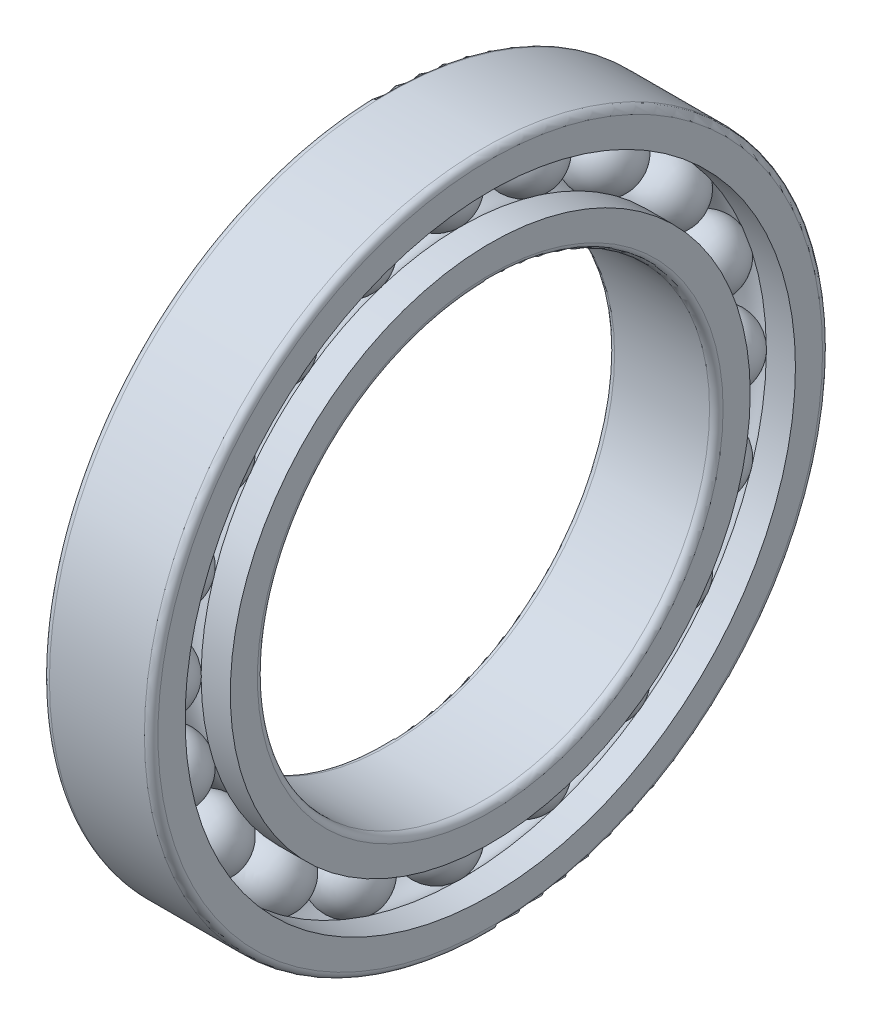
SolidWorks part; units mm, degrees
ref_plane "Plane1" through (0, 0, 0) normal (0, 0, 1) x (1, 0, 0)
ref_plane "Plane2" through (0, 0, 0) normal (0, 1, 0) x (1, 0, 0)
ref_plane "Plane3" through (0, 0, 0) normal (1, 0, 0) x (0, 0, -1)
sketch "Clipboard" plane through (0, 0, 0) normal (0, 0, 1) x (1, 0, 0)
  line L0 (-10, 0) -> (10, 0) construction
  line L1 (0, 0) -> (21.0122, -7.6478)
  line L2 (0, 0) -> (58.7308, 21.3763)
  line L3 (0, 0) -> (21.0122, -7.6478)
  line L4 (0, 0) -> (-22.3573, -0.3902)
  dimension "BallCLRad" = 62.5
sketch "CagSpiSke" plane through (0, 0, 0) normal (0, 0, 1) x (1, 0, 0)
  line L0 (0.75, 61.25) -> (0.75, 63.75)
  line L1 (0.75, 63.75) -> (-0.75, 63.75)
  line L2 (-0.75, 63.75) -> (-0.75, 61.25)
  line L3 (-0.75, 61.25) -> (0.75, 61.25)
  line L4 (-20.6375, 0) -> (20.6375, 0) construction
  line L5 (0, 0) -> (0, 23.7692) construction
  dimension "OD" = 127.5
  dimension "ID" = 122.5
revolve "CageSpine" add sketch "CagSpiSke" angle 0.001 about L4 reverse direction yes
ref_axis "Axis1" through (-50, 0, 0) along (1, 0, 0)
sketch "CagBalSke" plane through (0, 0, 0) normal (0, 0, 1) x (1, 0, 0)
  line L0 (-8.25, 62.5) -> (8.25, 62.5)
  line L1 (-1.905, 62.5) -> (1.905, 62.5) construction
  line L2 (-10, 0) -> (10, 0) construction
  line L3 (0, 0) -> (0, 24) construction
  arc A0 (8.25, 62.5) -> (-8.25, 62.5) centre (0, 62.5) cw
  dimension "BallCLRad" = 62.5
revolve "CageBall" [suppressed] add sketch "CagBalSke" angle 360 about L1 reverse direction yes
pattern_circular "CageBalls" [suppressed] count 20 every 18 about axis through (-50, 0, 0) along (1, 0, 0)
sketch "CagTrmODSke" plane through (0, 0, 0) normal (0, 0, 1) x (1, 0, 0)
  line L0 (8.251, 63.75) -> (8.251, 70.751)
  line L1 (8.251, 70.751) -> (-8.251, 70.751)
  line L2 (-8.251, 70.751) -> (-8.251, 63.75)
  line L3 (-8.251, 63.75) -> (8.251, 63.75)
  line L4 (-20.6375, 0) -> (20.6375, 0) construction
  line L5 (0, 0) -> (0, 25) construction
  dimension "Width" = 16.502
  dimension "ID" = 127.5
  dimension "OD" = 141.502
revolve "CageTrimOD" [suppressed] cut sketch "CagTrmODSke" angle 360 about L4 reverse direction yes
sketch "CagTrmIDSke" plane through (0, 0, 0) normal (0, 0, 1) x (1, 0, 0)
  line L0 (8.251, 54.251) -> (8.251, 61.25)
  line L1 (8.251, 61.25) -> (-8.251, 61.25)
  line L2 (-8.251, 61.25) -> (-8.251, 54.251)
  line L3 (-8.251, 54.251) -> (8.251, 54.251)
  line L4 (-20.6375, 0) -> (20.6375, 0) construction
  line L5 (0, 0) -> (0, 25) construction
  dimension "Width" = 16.502
  dimension "ID" = 108.502
  dimension "OD" = 122.5
revolve "CageTrimID" [suppressed] cut sketch "CagTrmIDSke" angle 360 about L4 reverse direction yes
sketch "BalSimSke" plane through (0, 0, 0) normal (0, 0, 1) x (1, 0, 0)
  line L0 (-10, 0) -> (10, 0) construction
  line L1 (-10, 62.5) -> (10, 62.5) construction
  line L2 (0, 0) -> (0, 23) construction
  circle A0 centre (0, 62.5) radius 7.5
  dimension "BallCLRad" = 62.5
  dimension "Ball_diameter" = 15
revolve "BallsSimplified" [suppressed] add sketch "BalSimSke" angle 360 about L0
sketch "BalDetSke" plane through (0, 0, 0) normal (0, 0, 1) x (1, 0, 0)
  line L0 (-7.5, 62.5) -> (7.5, 62.5)
  line L1 (-1.905, 62.5) -> (1.905, 62.5) construction
  line L2 (0, 0) -> (0, 25) construction
  arc A0 (7.5, 62.5) -> (-7.5, 62.5) centre (0, 62.5) cw
  dimension "BallCLRad" = 62.5
  dimension "Ball_diameter" = 15
revolve "BallDetailed" add sketch "BalDetSke" angle 360 about L1 reverse direction yes
sketch "InnRacSke" plane through (0, 0, 0) normal (0, 0, 1) x (1, 0, 0)
  line L0 (-5.5566, 57.5) -> (-12, 57.5)
  line L1 (-12, 57.5) -> (-12, 51.5)
  line L2 (-10.5, 50) -> (10.5, 50)
  line L3 (12, 51.5) -> (12, 57.5)
  line L4 (12, 57.5) -> (5.5566, 57.5)
  line L5 (-20.6375, 0) -> (20.6375, 0) construction
  line L6 (0, 0) -> (0, 30) construction
  arc A0 (-12, 51.5) -> (-10.5, 50) centre (-10.5, 51.5) ccw
  arc A1 (10.5, 50) -> (12, 51.5) centre (10.5, 51.5) ccw
  arc A2 (5.5566, 57.5) -> (-5.5566, 57.5) centre (0, 62.5) cw
  dimension "BallCLRad" = 62.5
  dimension "Fillet_radius" = 1.5
  dimension "Ball_diameter" = 14.95
  dimension "ID" = 100
  dimension "OD" = 115
  dimension "Width" = 24
revolve "InnerRace" add sketch "InnRacSke" angle 360 about L5 reverse direction yes
sketch "OutRacSke" plane through (0, 0, 0) normal (0, 0, 1) x (1, 0, 0)
  line L0 (-5.5566, 67.5) -> (-12, 67.5)
  line L1 (-12, 67.5) -> (-12, 73.5)
  line L2 (-10.5, 75) -> (10.5, 75)
  line L3 (12, 73.5) -> (12, 67.5)
  line L4 (12, 67.5) -> (5.5566, 67.5)
  line L5 (-20.6375, 0) -> (20.6375, 0) construction
  line L6 (0, 0) -> (0, 30) construction
  arc A0 (-12, 73.5) -> (-10.5, 75) centre (-10.5, 73.5) cw
  arc A1 (10.5, 75) -> (12, 73.5) centre (10.5, 73.5) cw
  arc A2 (5.5566, 67.5) -> (-5.5566, 67.5) centre (0, 62.5) ccw
  dimension "BallCLRad" = 62.5
  dimension "Fillet_radius" = 1.5
  dimension "Ball_diameter" = 14.95
  dimension "Width" = 24
revolve "OuterRace" add sketch "OutRacSke" angle 360 about L5 reverse direction yes
pattern_circular "BallsDetailed" count 20 every 18 about axis through (-50, 0, 0) along (1, 0, 0) of "BallDetailed"
equation "\"BallCLRad@Clipboard\" = ( \"OD@OutRacSke\" + \"ID@InnRacSke\" ) / 4"
equation "\"BallCLRad@BalSimSke\" = \"BallCLRad@Clipboard\""
equation "\"BallCLRad@BalDetSke\" = \"BallCLRad@Clipboard\""
equation "\"BallCLRad@InnRacSke\" = \"BallCLRad@Clipboard\""
equation "\"BallCLRad@OutRacSke\" = \"BallCLRad@Clipboard\""
equation "\"Ball_diameter@InnRacSke\" = \"Ball_diameter@BalDetSke\" - 0.05"
equation "\"Ball_diameter@OutRacSke\" = \"Ball_diameter@BalDetSke\" - 0.05"
equation "\"Ball_diameter@BalSimSke\" = \"Ball_diameter@BalDetSke\""
equation "\"Width@OutRacSke\" = \"Width@InnRacSke\""
equation "\"Fillet_radius@OutRacSke\" = \"Fillet_radius@InnRacSke\""
equation "\"Max_count@Clipboard\" = int( 3.14159265 / atn(( \"Ball_diameter@BalDetSke\" / 2) / sqr( \"BallCLRad@Clipboard\"  *  \"BallCLRad@Clipboard\" - ( \"Ball_diameter@BalDetSke\" / 2) *  ( \"Ball_diameter@BalDetSke\" / 2))))"
equation "\"Max_count@Clipboard\" = ((sgn( \"Max_count@Clipboard\" - \"Count@Clipboard\" )-1)*( \"Max_count@Clipboard\" - \"Count@Clipboard\" ))/-2+ \"Count@Clipboard\""
equation "\"Count@BallsDetailed\" = int( \"Show_count@Clipboard\" ) "
equation "\"Count@BallsDetailed\" = ((sgn( \"Count@BallsDetailed\" - \"Max_count@Clipboard\" )-1)*( \"Count@BallsDetailed\" - \"Max_count@Clipboard\" ))/-2+ \"Max_count@Clipboard\""
equation "\"Count@BallsDetailed\" = ((sgn( \"Count@BallsDetailed\" - \"Min_count@Clipboard\" )+1)*( \"Count@BallsDetailed\" - \"Min_count@Clipboard\"))/2 +\"Min_count@Clipboard\""
equation "\"Angle@BallsDetailed\" = 360.0 / \"Max_count@Clipboard\""
equation "\"BallCLRad@CagBalSke\" = \"BallCLRad@Clipboard\""
equation "\"Count@CageBalls\" = \"Count@BallsDetailed\""
equation "\"Angle@CageBalls\" = \"Angle@BallsDetailed\""
equation "\"Angle@CageSpine\" =  \"Angle@CageBalls\" * ( \"Count@CageBalls\" -1 + int( \"Count@CageBalls\" / \"Max_count@Clipboard\" ) )  + 0.001 -  int( \"Count@CageBalls\" / \"Max_count@Clipboard\" ) * 0.001"
equation "\"Angle@CageSpine\" =  \"Angle@CageSpine\" * int( \"Min_count@Clipboard\" / 2) + int(1 / \"Min_count@Clipboard\")  * 0.001"
equation "\"CageWallOD@CagBalSke\" =  \"Ball_diameter@BalDetSke\" * 1.1"
equation "\"Thickness@CagSpiSke\" =  \"Ball_diameter@BalDetSke\" * 0.1"
equation "\"OD@CagTrmODSke\" = \"BallCLRad@Clipboard\" * 2 + \"CageWallOD@CagBalSke\" + 0.002"
equation "\"ID@CagTrmODSke\" = \"BallCLRad@Clipboard\" * 2 + \"Ball_diameter@BalDetSke\" / 6"
equation "\"OD@CagTrmIDSke\" = \"BallCLRad@Clipboard\" * 2 - \"Ball_diameter@BalDetSke\" / 6"
equation "\"ID@CagTrmIDSke\" = \"BallCLRad@Clipboard\" * 2 - \"CageWallOD@CagBalSke\" + 0.002"
equation "\"OD@CagSpiSke\" = \"ID@CagTrmODSke\""
equation "\"ID@CagSpiSke\" = \"OD@CagTrmIDSke\""
equation "\"Width@CagTrmODSke\" = \"CageWallOD@CagBalSke\" + 0.002"
equation "\"Width@CagTrmIDSke\" = \"CageWallOD@CagBalSke\" + 0.002"
